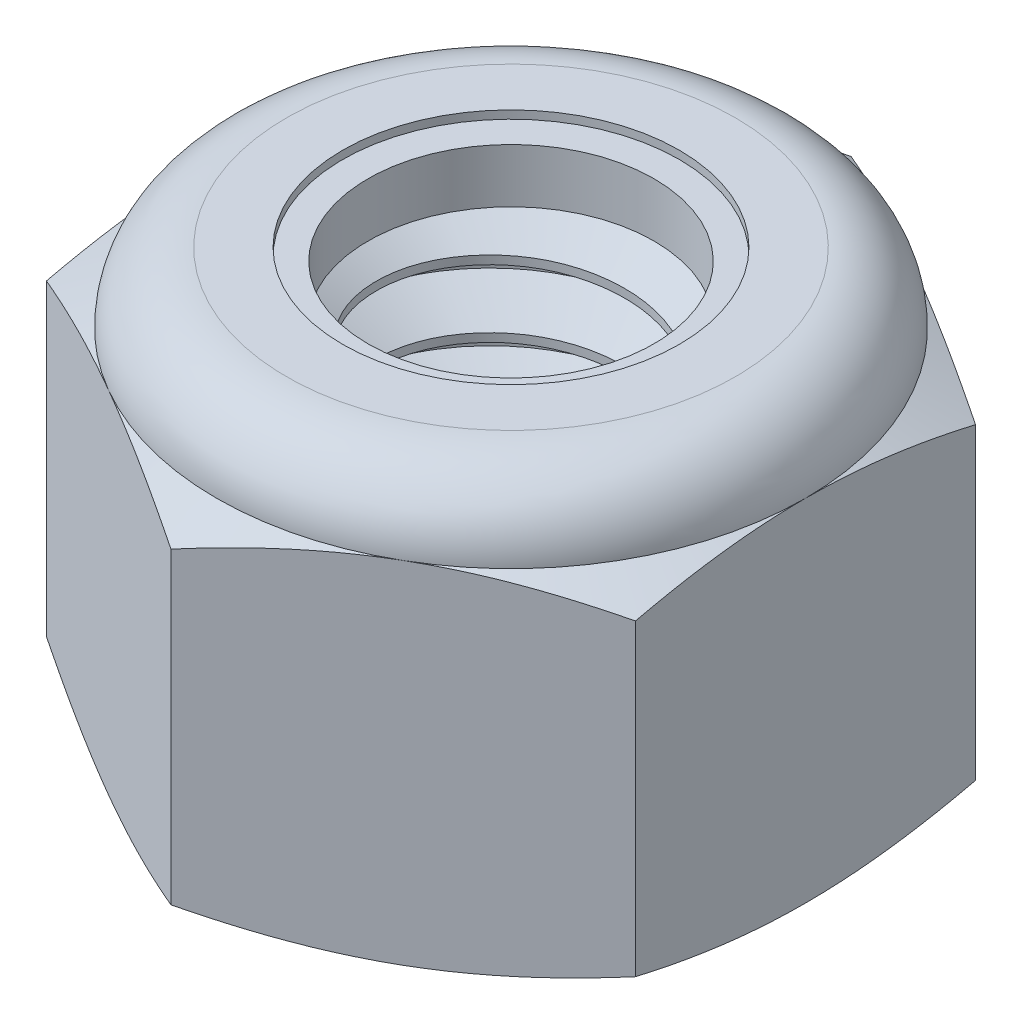
SolidWorks part; units mm, degrees
ref_plane "Front" through (0, 0, 0) normal (0, 0, 1) x (1, 0, 0)
ref_plane "Top" through (0, 0, 0) normal (0, 1, 0) x (1, 0, 0)
ref_plane "Right" through (0, 0, 0) normal (1, 0, 0) x (0, 0, -1)
sketch "Sketch1" plane through (0, 0, 0) normal (1, 0, 0) x (0, 0, -1)
  line L0 (0, 0) -> (0, 7.9375) construction
  line L1 (5.5562, 0) -> (-5.5562, 0) construction
  line L2 (-3.175, 7.9375) -> (3.175, 7.9375) construction
  line L3 (3.175, 7.9375) -> (3.175, 6.6675) construction
  point P9 (-3.175, 7.9375)
  point P10 (3.175, 7.9375)
  point P11 (5.5562, 0)
  dimension "Height" = 7.9375
  dimension "Hex Flats" = 11.1125
  dimension "Thread Dia" = 6.35
  dimension "Thread Pitch" = 1.27
sketch "Sketch13" plane through (0, 0, 0) normal (0, 1, 0) x (1, 0, 0)
  line L1 (0, 6.4158) -> (-5.5563, 3.2079)
  line L2 (-5.5563, 3.2079) -> (-5.5562, -3.2079)
  line L3 (-5.5562, -3.2079) -> (0, -6.4158)
  line L4 (0, -6.4158) -> (5.5563, -3.2079)
  line L5 (5.5563, -3.2079) -> (5.5563, 3.2079)
  line L6 (5.5563, 3.2079) -> (0, 6.4158)
  circle A0 centre (0, 0) radius 5.5562 construction
  circle A1 centre (0, 0) radius 3.175
  point P11 (0, -3.175)
  point P13 (0, 3.175)
extrude "Extrude1" add sketch "Sketch13" along normal up to vertex (7.9375 mm away) up to point (0, 7.9375, 0)
sketch "Sketch5" plane through (0, 0, 0) normal (1, 0, 0) x (0, 0, -1)
  line L0 (0, 0) -> (5.5562, 0)
  line L1 (5.5562, 0) -> (6.4158, 0.4008)
  line L2 (6.4158, 0.4008) -> (6.4158, 6.2138)
  line L3 (6.4158, 6.2138) -> (5.5562, 6.6146)
  line L4 (4.2333, 7.9375) -> (4.2333, 9.2075)
  line L5 (4.2333, 9.2075) -> (7.6858, 9.2075)
  line L6 (7.6858, 9.2075) -> (7.6858, -1.27)
  line L7 (7.6858, -1.27) -> (0, -1.27)
  line L8 (0, -1.27) -> (0, 0)
  line L9 (5.5562, 6.6146) -> (5.5562, 0) construction
  line L12 (6.4158, 7.9375) -> (6.4158, 0) construction
  line L13 (6.4158, 3.9688) -> (7.6858, 3.9688) construction
  line L15 (0, 0) -> (0, 9.2075) construction
  line L18 (5.5562, 0) -> (-5.5562, 0) construction
  line L19 (3.2079, 7.9375) -> (6.4158, 7.9375) construction
  line L20 (0, 9.2075) -> (4.2333, 9.2075) construction
  line L21 (3.2079, 0) -> (6.4158, 0) construction
  arc A0 (5.5562, 6.6146) -> (4.2333, 7.9375) centre (4.2333, 6.6146) ccw
  dimension "D1" = 25
  dimension "D2" = 1.27
  dimension "D4" = 1.3229
revolve "Cut-Revolve3" cut sketch "Sketch5" angle 360 about L15
sketch "Sketch4" plane through (0, 0, 0) normal (1, 0, 0) x (0, 0, -1)
  line L0 (0, 6.6146) -> (3.4925, 6.6146)
  line L1 (3.4925, 6.6146) -> (0, 4.986)
  line L3 (0, 1.6286) -> (3.4925, 0)
  line L4 (3.4925, 0) -> (0, 0)
  line L5 (0, 0) -> (0, 6.6146) construction
  line L10 (0, 0) -> (0, 7.9375) construction
  line L11 (0, 1.6286) -> (0, 0)
  line L12 (0, 6.6146) -> (0, 4.986)
  line L13 (4.8119, 6.6146) -> (0, 6.6146) construction
  dimension "D1" = 25
  dimension "D2" = 6.985
sketch "Sketch6" plane through (0, 0, 0) normal (1, 0, 0) x (0, 0, -1)
  line L0 (0, 6.6146) -> (5.4039, 6.6146)
  line L1 (4.2333, 7.7851) -> (2.1167, 7.7851)
  line L2 (0, 9.2075) -> (0, 6.6146)
  line L3 (2.1167, 9.2075) -> (0, 9.2075)
  line L4 (0, 9.2075) -> (4.2333, 9.2075) construction
  line L5 (0, 0) -> (0, 9.2075) construction
  line L6 (0, 9.2075) -> (0, 0) construction
  line L7 (2.1167, 7.7851) -> (2.1167, 9.2075)
  line L8 (4.2333, 7.9375) -> (4.2333, 7.7851) construction
  line L9 (2.1167, 7.7851) -> (0, 7.7851) construction
  line L10 (0, 7.7851) -> (0, 4.986) construction
  arc A0 (5.4039, 6.6146) -> (4.2333, 7.7851) centre (4.2333, 6.6146) ccw
  arc A1 (5.5562, 6.6146) -> (4.2333, 7.9375) centre (4.2333, 6.6146) ccw construction
  dimension "D1" = 0.1524
revolve "Cut-Revolve4" cut sketch "Sketch6" angle 360 about L6
revolve "Cut-Revolve2" cut sketch "Sketch4" angle 360 about L5
sketch "Sketch7" plane through (0, 0, 0) normal (1, 0, 0) x (0, 0, -1)
  line L0 (2.6988, 6.6908) -> (5.325, 6.6908)
  line L1 (4.2333, 7.7089) -> (2.6988, 7.7089)
  line L2 (2.6988, 7.7089) -> (2.6988, 6.6908)
  line L3 (2.6988, 6.6908) -> (0, 6.6908) construction
  line L4 (0, 6.6908) -> (0, 7.7089) construction
  line L5 (0, 7.7089) -> (2.6988, 7.7089) construction
  line L6 (2.6988, 6.6908) -> (2.6988, 6.6146) construction
  line L7 (0, 6.6146) -> (5.4039, 6.6146) construction
  line L8 (4.2333, 7.7089) -> (4.2333, 7.7851) construction
  arc A0 (5.325, 6.6908) -> (4.2333, 7.7089) centre (4.2333, 6.6146) ccw
  arc A2 (5.4039, 6.6146) -> (4.2333, 7.7851) centre (4.2333, 6.6146) ccw construction
  point P15 (2.6988, 7.7089)
  point P18 (-3.466, 7.7089)
  point P19 (3.466, 7.7089)
  dimension "D1" = 0.0762
  dimension "D2" = 5.3975
revolve "Revolve2" add sketch "Sketch7" angle 360 about L4
sketch "Sketch2" plane through (0, 0, 0) normal (1, 0, 0) x (0, 0, -1)
  line L0 (-3.175, 0) -> (-3.175, 6.6146) construction
  line L1 (0, 0) -> (3.175, 0)
  line L2 (0, 0) -> (0, 6.6146)
  line L3 (0, 6.6146) -> (3.175, 6.6146)
  line L4 (3.175, 0) -> (3.175, 6.6146)
  line L6 (4.8119, 6.6146) -> (5.5562, 6.6146) construction
  line L7 (0, -3.175) -> (0, 0) construction
revolve "Revolve1" add sketch "Sketch2" angle 360 about L7
sketch "Sketch9" plane through (0, 0, 0) normal (1, 0, 0) x (0, 0, -1)
  line L0 (3.3125, 7.8052) -> (3.3125, 6.5352) construction
  line L1 (3.3125, 6.5352) -> (2.2126, 7.1702) construction
  line L2 (2.2126, 7.1702) -> (3.3125, 7.8052) construction
  line L3 (2.3501, 7.2496) -> (2.3501, 7.0908) construction
  line L4 (3.175, 7.7258) -> (3.175, 6.6146) construction
  line L5 (2.2126, 7.1702) -> (2.3501, 7.1702) construction
  line L6 (3.175, 7.1702) -> (3.3125, 7.1702) construction
  line L7 (3.2437, 7.1702) -> (3.2437, 7.7655) construction
  line L8 (3.3125, 6.5352) -> (3.2437, 7.7655)
  line L9 (3.2437, 7.7655) -> (2.3501, 7.2496)
  line L10 (2.3501, 7.2496) -> (2.3501, 7.0908)
  line L11 (2.3501, 7.0908) -> (3.3125, 6.5352)
  dimension "D1" = 1.27
  dimension "D2" = 0.1588
sketch "Sketch10" plane through (0, 6.6146, 0) normal (0, 1, 0) x (1, 0, 0)
  circle A1 centre (0, 0) radius 3.175
  circle A2 centre (0, 0) radius 3.175
  dimension "D1" = 0
curve "Helix/Spiral1" pitch 1.27 height 9.2075 turns 7.25
sweep "Cut-Sweep1" cut profiles "Sketch9" path "Helix/Spiral1"
sketch "Sketch11" plane through (0, 0, 0) normal (1, 0, 0) x (0, 0, -1)
  line L0 (0, 0) -> (0, 7.9375) construction
  line L1 (5.5562, 0) -> (-5.5562, 0) construction
  line L4 (0, 7.9375) -> (0, 0) construction
  line L5 (0, 3.9688) -> (3.175, 3.9688) construction
  line L6 (0, 0) -> (3.4925, 0)
  line L7 (0, 1.6286) -> (0, 0)
  line L8 (3.4925, 0) -> (0, 1.6286)
  dimension "D1" = 6.985
  dimension "D2" = 25
revolve "Revolve3" add sketch "Sketch11" angle 360 about L4
sketch "Sketch12" plane through (0, 0, 0) normal (1, 0, 0) x (0, 0, -1)
  line L0 (3.4925, 6.6146) -> (0, 6.6146)
  line L1 (0, 6.6146) -> (0, 0)
  line L2 (0, 0) -> (3.4925, 0)
  line L3 (5.5562, 0) -> (-5.5562, 0) construction
  line L4 (3.4925, 0) -> (3.4925, 6.6146)
  line L5 (-3.4925, 0) -> (3.4925, 0) construction
revolve "Revolve4" add sketch "Sketch12" angle 360 about L0
combine bodies "Combine1" bodies to combine 136 133
equation "\"D4@Sketch5\" = \"Height@Sketch1\" / 6"
equation "\"D1@Sketch9\" = \"Thread Pitch@Sketch1\""
equation "\"D2@Sketch9\" = \"Thread Pitch@Sketch1\" / 8"
equation "\"D4@Helix/Spiral1\" = \"Thread Pitch@Sketch1\""
equation "\"D3@Helix/Spiral1\" = \"Thread Pitch@Sketch1\" + \"Height@Sketch1\""
equation "\"D2@Sketch4\" = \"Thread Dia@Sketch1\" * 1.1"
equation "\"D1@Sketch11\" = \"Thread Dia@Sketch1\" * 1.1"
equation "\"D2@Sketch7\" = \"Thread Dia@Sketch1\" * .85"
